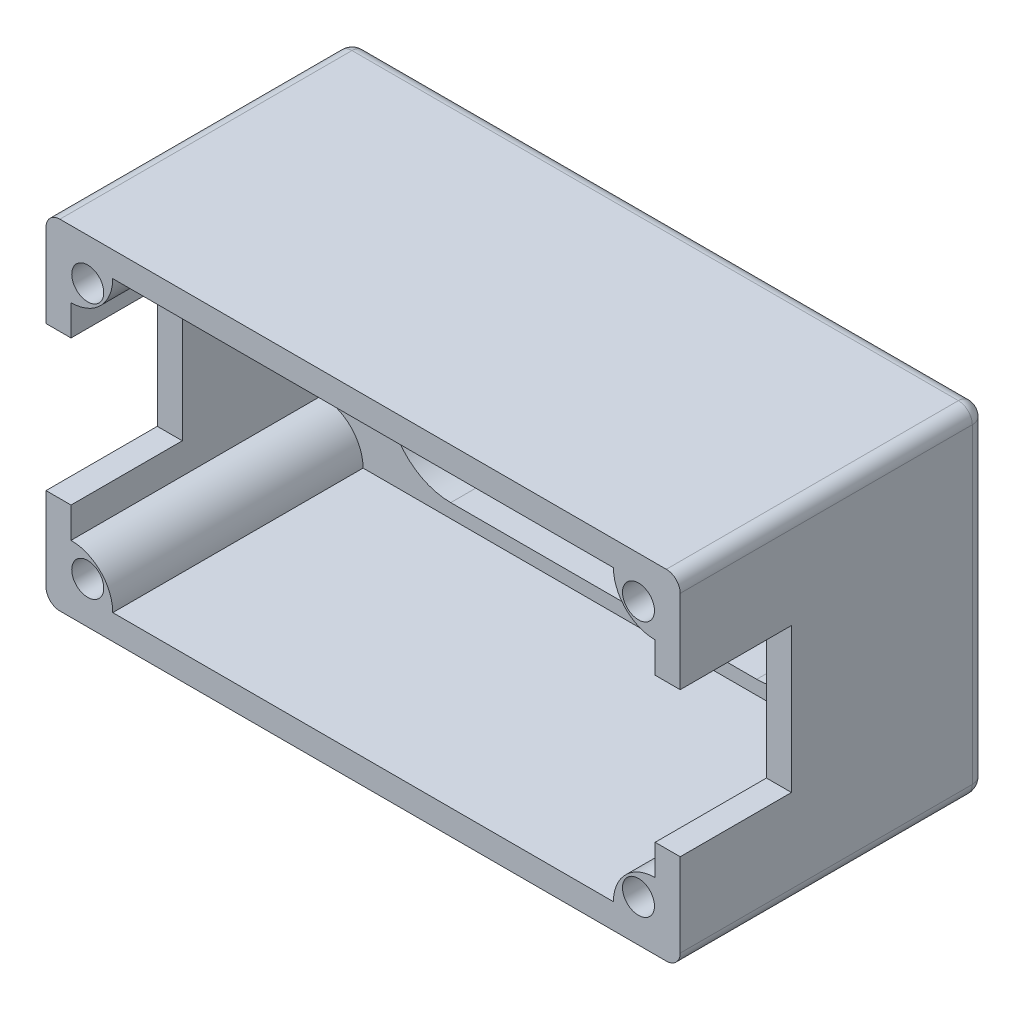
SolidWorks part; units mm, degrees
ref_plane "前视基准面" through (0, 0, 0) normal (0, 0, 1) x (1, 0, 0)
ref_plane "上视基准面" through (0, 0, 0) normal (0, 1, 0) x (1, 0, 0)
ref_plane "右视基准面" through (0, 0, 0) normal (1, 0, 0) x (0, 0, -1)
sketch "草图1" plane through (0, 0, 0) normal (0, 0, 1) x (1, 0, 0)
  line L1 (-11.4, 6.1) -> (11.4, 6.1)
  line L2 (-11.4, 6.1) -> (-11.4, -6.1)
  line L3 (-11.4, -6.1) -> (11.4, -6.1)
  line L4 (11.4, 6.1) -> (11.4, -6.1)
  line L5 (-11.4, 6.1) -> (11.4, -6.1) construction
  line L6 (-11.4, -6.1) -> (11.4, 6.1) construction
  point P0 (0, 0)
  dimension "D1" = 22.8
  dimension "D2" = 12.2
extrude "凸台-拉伸1" add sketch "草图1" along normal blind 11
sketch "草图2" plane through (0, 0, 11) normal (0, 0, 1) x (1, 0, 0)
  line L0 (11.4, 6.1) -> (-11.4, 6.1) construction
  line L1 (-10.5, 5.2) -> (10.5, 5.2)
  line L2 (-10.5, 5.2) -> (-10.5, -5.2)
  line L3 (-10.5, -5.2) -> (10.5, -5.2)
  line L4 (10.5, 5.2) -> (10.5, -5.2)
  line L5 (-11.4, 6.1) -> (-11.4, -6.1) construction
  line L6 (-11.4, -6.1) -> (11.4, -6.1) construction
  line L7 (11.4, -6.1) -> (11.4, 6.1) construction
  dimension "D1" = 0.9
  dimension "D2" = 0.9
  dimension "D3" = 0.9
  dimension "D4" = 0.9
extrude "切除-拉伸1" cut sketch "草图2" against normal blind 9
sketch "草图3" plane through (0, 0, 2) normal (0, 0, 1) x (1, 0, 0)
  line L0 (10.5, -5.2) -> (10.5, 5.2) construction
  line L1 (10.5, 5.2) -> (-10.5, 5.2) construction
  line L2 (10.5, -5.2) -> (10.5, 5.2) construction
  line L3 (-10.5, -5.2) -> (10.5, -5.2) construction
  line L4 (-10.5, 5.2) -> (-10.5, -5.2) construction
  circle A0 centre (9.9, 4.6) radius 0.575
  circle A1 centre (-9.9, -4.6) radius 0.575
  circle A2 centre (9.9, -4.6) radius 0.575
  circle A3 centre (-9.9, 4.6) radius 0.575
  dimension "D1" = 1.15
  dimension "D5" = 1.15
  dimension "D7" = 1.15
  dimension "D10" = 0.6
  dimension "D11" = 1.15
  dimension "D2" = 0.6
  dimension "D3" = 0.6
  dimension "D4" = 19.8
  dimension "D6" = 0.6
  dimension "D8" = 0.6
  dimension "D9" = 0.6
  dimension "D12" = 0.6
sketch "草图4" plane through (0, 0, 11) normal (0, 0, 1) x (1, 0, 0)
  line L0 (-11.4, 6.1) -> (-11.4, -6.1) construction
  line L1 (-11.4, 2.6) -> (-10.5, 2.6)
  line L2 (-11.4, 2.6) -> (-11.4, -2.6)
  line L3 (-11.4, -2.6) -> (-10.5, -2.6)
  line L4 (-10.5, 2.6) -> (-10.5, -2.6)
  line L5 (-10.5, 5.2) -> (-10.5, -5.2) construction
  line L6 (11.4, 6.1) -> (-11.4, 6.1) construction
  line L8 (-11.4, -6.1) -> (11.4, -6.1) construction
  dimension "D1" = 3.5
  dimension "D2" = 3.5
extrude "切除-拉伸2" cut sketch "草图4" against normal blind 4
fillet "圆角1" radius 0.5 4 edges at (0, 6.1, 0) (-11.4, 0, 0) (0, -6.1, 0) (11.4, 0, 0)
sketch "草图7" plane through (0, 0, 2) normal (0, 0, 1) x (1, 0, 0)
  line L0 (-5.85, -2.45) -> (5.15, -2.45) construction
  line L1 (-5.85, -0.2) -> (5.15, -0.2)
  line L2 (-5.85, -4.7) -> (5.15, -4.7)
  line L3 (-10.5, -5.2) -> (10.5, -5.2) construction
  line L5 (10.5, -5.2) -> (10.5, 5.2) construction
  arc A0 (-5.85, -0.2) -> (-5.85, -4.7) centre (-5.85, -2.45) ccw
  arc A1 (5.15, -4.7) -> (5.15, -0.2) centre (5.15, -2.45) ccw
  point P2 (-0.35, -2.45)
  point P7 (-8.1, -2.45)
  point P8 (7.4, -2.45)
  dimension "D2" = 15.5
  dimension "D1" = 11
  dimension "D3" = 0.5
  dimension "D4" = 10.85
extrude "切除-拉伸5" cut sketch "草图7" against normal blind 2
fillet "圆角2" radius 0.5 8 edges at (11.2536, 5.9536, 0.1464) (11.2536, -5.9536, 0.1464) (-11.2536, -5.9536, 0.1464) (-11.2536, 5.9536, 0.1464) (11.4, 6.1, 5.75) (11.4, -6.1, 5.75) (-11.4, -6.1, 5.75) (-11.4, 6.1, 5.75)
sketch "草图8" plane through (0, 0, 11) normal (0, 0, 1) x (1, 0, 0)
  line L0 (10.5, -5.2) -> (10.5, 5.2) construction
  line L1 (10.5, 2.6) -> (11.4, 2.6)
  line L2 (10.5, 2.6) -> (10.5, -2.6)
  line L3 (10.5, -2.6) -> (11.4, -2.6)
  line L4 (11.4, 2.6) -> (11.4, -2.6)
  line L5 (11.4, -5.6) -> (11.4, 5.6) construction
  line L6 (10.9, 6.1) -> (-10.9, 6.1) construction
  line L7 (-10.9, -6.1) -> (10.9, -6.1) construction
  dimension "D1" = 3.5
  dimension "D2" = 3.5
extrude "切除-拉伸6" cut sketch "草图8" against normal blind 4
sketch "草图10" plane through (0, 0, 2) normal (0, 0, 1) x (1, 0, 0)
  line L0 (-10.5, -2.6) -> (-10.5, -5.2) construction
  line L1 (-10.5, -5.2) -> (10.5, -5.2) construction
  line L2 (-10.5, 5.2) -> (-10.5, -5.2) construction
  line L3 (-10.5, -5.2) -> (10.5, -5.2) construction
  line L4 (10.5, 5.2) -> (-10.5, 5.2) construction
  line L5 (10.5, -5.2) -> (10.5, 5.2) construction
  line L6 (10.5, -5.2) -> (10.5, -2.6) construction
  line L7 (10.5, 5.2) -> (-10.5, 5.2) construction
  line L8 (-10.5, 5.2) -> (-10.5, 2.6) construction
  line L9 (-10.5, 3.7) -> (-10.5, 5.2)
  line L10 (10.5, 2.6) -> (10.5, 5.2) construction
  line L11 (9, 5.2) -> (10.5, 5.2)
  line L12 (10.5, 5.2) -> (10.5, 3.7)
  line L13 (-10.5, 5.2) -> (-9, 5.2)
  line L14 (10.5, -3.7) -> (10.5, -5.2)
  line L15 (10.5, -5.2) -> (9, -5.2)
  line L16 (-10.5, -3.7) -> (-10.5, -5.2)
  line L17 (-10.5, -5.2) -> (-9, -5.2)
  arc A0 (-10.5, -3.7) -> (-9, -5.2) centre (-10.5, -5.2) cw
  arc A1 (10.5, -3.7) -> (9, -5.2) centre (10.5, -5.2) ccw
  arc A2 (-9, 5.2) -> (-10.5, 3.7) centre (-10.5, 5.2) cw
  arc A3 (9, 5.2) -> (10.5, 3.7) centre (10.5, 5.2) ccw
  dimension "D3" = 1.5
  dimension "D6" = 1.5
  dimension "D7" = 1.5
  dimension "D9" = 1.5
  dimension "D10" = 1.5
  dimension "D12" = 1.5
  dimension "D1" = 1.5
  dimension "D2" = 1.5
  dimension "D4" = 1.5
  dimension "D5" = 1.5
  dimension "D8" = 1.5
  dimension "D11" = 1.5
extrude "凸台-拉伸2" add sketch "草图10" along normal blind 9
extrude "切除-拉伸8" cut sketch "草图3" along normal through all and the other way through all
sketch "草图9" plane through (0, 0, 0) normal (0, 0, -1) x (-1, 0, 0)
  circle A0 centre (-9.9, 4.6) radius 1
  circle A1 centre (9.9, 4.6) radius 1
  circle A2 centre (9.9, -4.6) radius 1
  circle A3 centre (-9.9, -4.6) radius 1
  dimension "D1" = 2
  dimension "D2" = 2
  dimension "D3" = 2
  dimension "D4" = 2
extrude "切除-拉伸9" cut sketch "草图9" against normal blind 0.5
